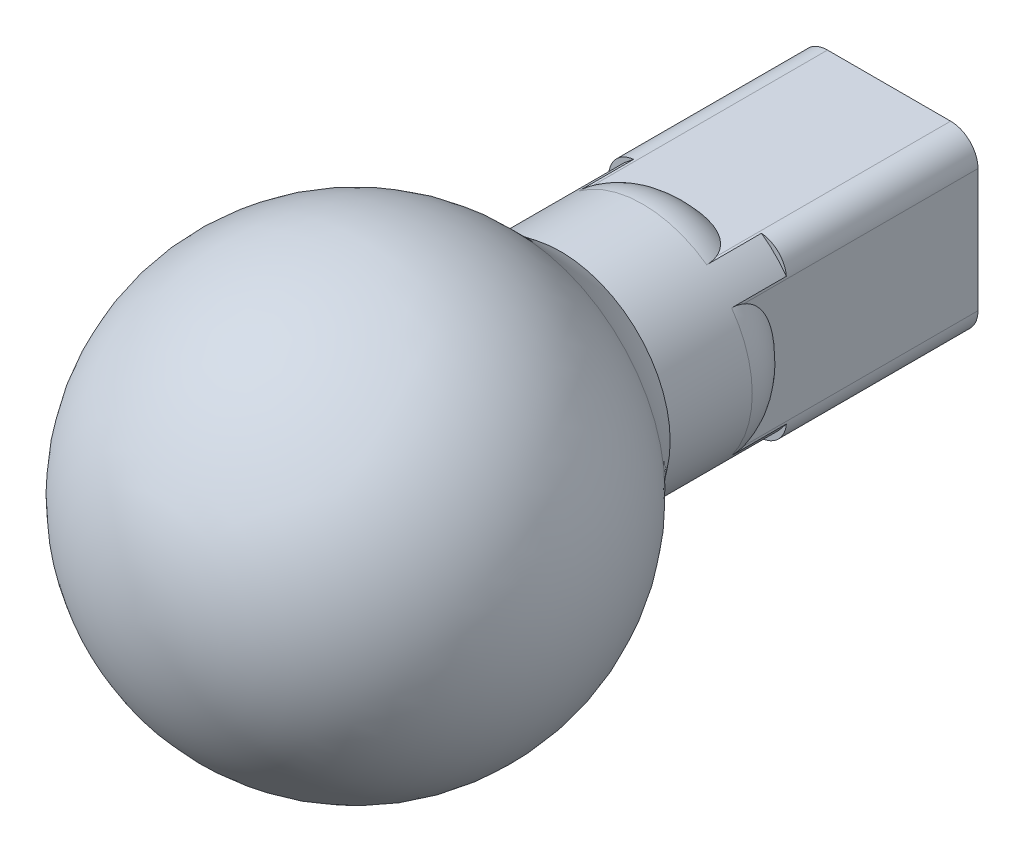
SolidWorks part; units mm, degrees
ref_plane "Front" through (0, 0, 0) normal (0, 0, 1) x (1, 0, 0)
ref_plane "Top" through (0, 0, 0) normal (0, 1, 0) x (1, 0, 0)
ref_plane "Right" through (0, 0, 0) normal (1, 0, 0) x (0, 0, -1)
sketch "Sketch1" plane through (0, 0, 0) normal (0, 0, 1) x (1, 0, 0)
  line L1 (3.25, -3.25) -> (-3.25, -3.25)
  line L2 (3.25, -3.25) -> (3.25, 3.25)
  line L3 (3.25, 3.25) -> (-3.25, 3.25)
  line L4 (-3.25, -3.25) -> (-3.25, 3.25)
  line L5 (3.25, -3.25) -> (-3.25, 3.25) construction
  line L6 (3.25, 3.25) -> (-3.25, -3.25) construction
  point P0 (0, 0)
  dimension "D1" = 6.5
  dimension "D2" = 6.5
extrude "Boss-Extrude1" add sketch "Sketch1" along normal blind 7
sketch "Sketch2" plane through (0, 0, 7) normal (0, 0, 1) x (1, 0, 0)
  circle A0 centre (0, 0) radius 4
  dimension "D1" = 8
extrude "Boss-Extrude2" add sketch "Sketch2" along normal blind 5
sketch "Sketch3" plane through (0, 0, 0) normal (0, 1, 0) x (1, 0, 0)
  line L0 (0, 0) -> (0, -30)
  line L1 (-4, -12) -> (4, -12) construction
  circle A0 centre (0, -19.5) radius 8
  dimension "D2" = 16
  dimension "D1" = 7.5
  dimension "D3" = 30
revolve "Revolve1" add sketch "Sketch3" angle 360 about L0 region at (-3.3953, 0, 19.5)
fillet "Fillet1" radius 10 1 edges at (2.7839, 0, 12)
fillet "Fillet2" radius 2 4 edges at (0, 4, 7) (-4, 0, 7) (0, -4, 7) (4, 0, 7)
fillet "Fillet3" radius 1 4 edges at (3.25, -3.25, 3.5) (3.25, 3.25, 3.5) (-3.25, -3.25, 3.5) (-3.25, 3.25, 3.5)
